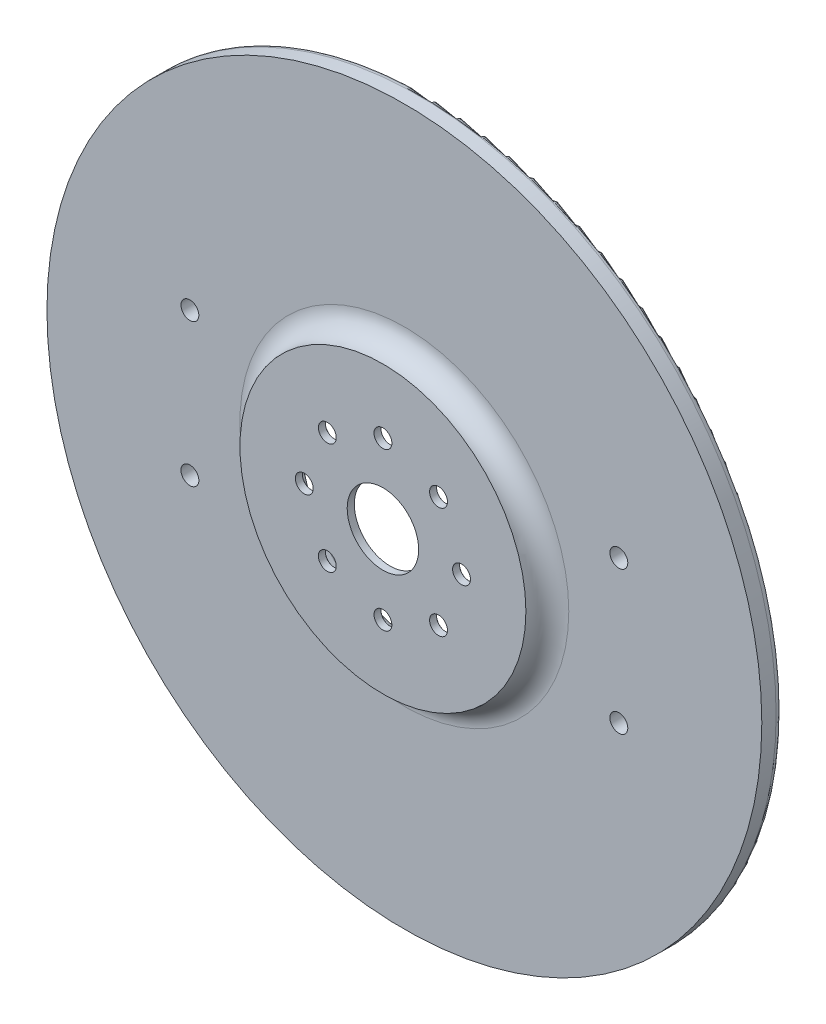
SolidWorks part; units mm, degrees
ref_plane "前视基准面" through (0, 0, 0) normal (0, 0, 1) x (1, 0, 0)
ref_plane "上视基准面" through (0, 0, 0) normal (0, 1, 0) x (1, 0, 0)
ref_plane "右视基准面" through (0, 0, 0) normal (1, 0, 0) x (0, 0, -1)
sketch "草图1" plane through (0, 0, 0) normal (0, 0, 1) x (1, 0, 0)
  circle A0 centre (0, 0) radius 50
  dimension "D1" = 100
extrude "凸台-拉伸1" add sketch "草图1" along normal blind 3
sketch "草图2" plane through (0, 0, 0) normal (0, 0, -1) x (-1, 0, 0)
  line L0 (0, 0) -> (0, -66.2427) construction
  line L1 (0, 0) -> (-41.6854, 0) construction
hole_wizard "Ø2.5mm 暗销孔1" positions "草图3" profile "草图4" hole size "Ø2.5" standard "ISO" end condition through all
sketch "草图3" plane through (0, 0, 0) normal (0, 0, -1) x (-1, 0, 0)
  line L3 (0, 200000) -> (0, -200066.2427) construction
  line L4 (200000, 0) -> (-200041.6854, 0) construction
  line L5 (0, 0) -> (0, -17.8195) construction
  line L7 (0, 0) -> (-57.4119, 0) construction
  point P0 (-30, 10)
  point P46 (0, 0)
  point P47 (0, 0)
  point P48 (-30, -10)
  point P49 (0, 0)
  point P50 (30, -10)
  point P51 (30, 10)
  point P52 (0, 0)
  point P53 (0, 0)
  dimension "D5" = 30
  dimension "D6" = 10
sketch "草图4" plane through (30, 10, 0) normal (1, 0, 0) x (0, 1, 0)
  line L0 (0, 0) -> (0, 3)
  line L1 (0, 3) -> (1.25, 3)
  line L2 (1.25, 3) -> (1.25, 0.025)
  line L3 (1.25, 0.025) -> (1.275, 0)
  line L5 (1.275, 0) -> (0, 0)
  line L6 (-1.25, 0.025) -> (-1.275, 0) construction
  line L11 (0, -6.35) -> (0, 107.95) construction
  dimension "通孔孔直径" = 2.5
  dimension "通孔孔深度" = 3
  dimension "近端锥形沉头孔直径" = 2.55
  dimension "近端锥形沉头孔角度" = 90
sketch "草图5" plane through (0, 0, 3) normal (0, 0, 1) x (1, 0, 0)
  circle A0 centre (0, 0) radius 20
  dimension "D1" = 40
extrude "凸台-拉伸2" add sketch "草图5" along normal blind 3
sketch "草图6" plane through (0, 0, 0) normal (0, 0, -1) x (-1, 0, 0)
  circle A0 centre (0, 0) radius 17
  dimension "D1" = 34
extrude "切除-拉伸1" cut sketch "草图6" against normal blind 5
hole_wizard "Ø2.5mm 暗销孔2" positions "草图8" profile "草图9" hole size "Ø2.5" standard "ISO" end condition through all
sketch "草图8" plane through (0, 0, 5) normal (0, 0, -1) x (-1, 0, 0)
  line L0 (200000, 0) -> (-200041.6854, 0) construction
  point P60 (-11, 0)
  point P72 (-7.7782, 7.7782)
  point P73 (0, 11)
  point P74 (7.7782, 7.7782)
  point P75 (11, 0)
  point P76 (7.7782, -7.7782)
  point P77 (0, -11)
  point P78 (-7.7782, -7.7782)
  dimension "D1" = 11
sketch "草图9" plane through (11, 0, 5) normal (1, 0, 0) x (0, 1, 0)
  line L0 (0, 0) -> (0, 1)
  line L1 (0, 1) -> (1.25, 1)
  line L2 (1.25, 1) -> (1.25, 0.025)
  line L3 (1.25, 0.025) -> (1.275, 0)
  line L5 (1.275, 0) -> (0, 0)
  line L6 (-1.25, 0.025) -> (-1.275, 0) construction
  line L11 (0, -6.35) -> (0, 107.95) construction
  dimension "通孔孔直径" = 2.5
  dimension "通孔孔深度" = 1
  dimension "近端锥形沉头孔直径" = 2.55
  dimension "近端锥形沉头孔角度" = 90
sketch "草图10" plane through (0, 0, 5) normal (0, 0, -1) x (-1, 0, 0)
  circle A0 centre (0, 0) radius 5
  dimension "D1" = 10
extrude "切除-拉伸2" cut sketch "草图10" against normal blind 5
fillet "圆角1" radius 1 6 edges at (50, 0, 0) (-31.275, 10, 0) (-31.275, -10, 0) (28.725, -10, 0) (28.725, 10, 0) (-17, 0, 0)
fillet "圆角3" radius 3 1 edges at (20, 0, 3)
